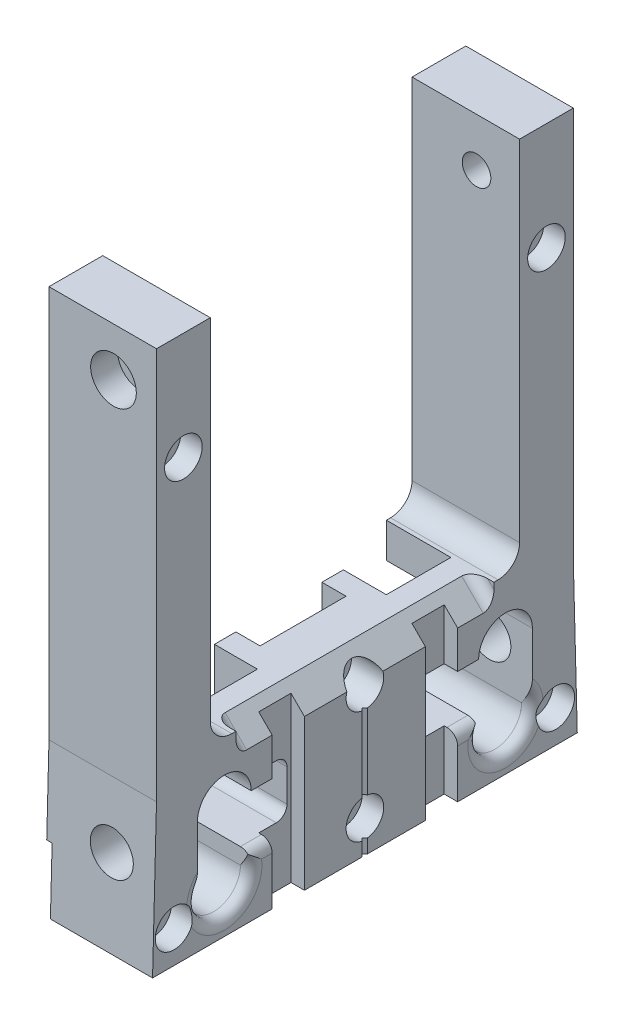
SolidWorks part; units mm, degrees
material "Nylatron"
ref_plane "Front Plane" through (0, 0, 0) normal (0, 0, 1) x (1, 0, 0)
ref_plane "Top Plane" through (0, 0, 0) normal (0, 1, 0) x (1, 0, 0)
ref_plane "Right Plane" through (0, 0, 0) normal (1, 0, 0) x (0, 0, -1)
sketch "Sketch1" plane through (0, 0, 0) normal (0, 0, 1) x (1, 0, 0)
  line L1 (-15.875, 80.1688) -> (15.875, 80.1688)
  line L2 (-15.875, 80.1688) -> (-15.875, -80.1688)
  line L3 (-15.875, -80.1688) -> (15.875, -80.1688)
  line L4 (15.875, 80.1688) -> (15.875, -80.1688)
  line L5 (-15.875, 80.1688) -> (15.875, -80.1688) construction
  line L6 (-15.875, -80.1688) -> (15.875, 80.1688) construction
  point P0 (0, 0)
  dimension "Width" = 31.75
  dimension "Height" = 160.3375
extrude "Extrude1" add sketch "Sketch1" along normal mid plane 125.4125
sketch "Sketch2" plane through (15.875, 0, 0) normal (1, 0, 0) x (0, 0, -1)
  line L0 (-62.7063, -80.1688) -> (-61.5423, -35.7188)
  line L1 (-62.7063, 80.1688) -> (62.7063, 80.1688) construction
  line L3 (62.7063, -80.1688) -> (61.5423, -35.7188)
  line L4 (62.7063, -80.1688) -> (62.7063, 80.1688) construction
  line L5 (-62.7063, -80.1688) -> (62.7063, -80.1688) construction
  line L6 (-61.5423, -35.7188) -> (-61.5423, 80.1688)
  line L7 (61.5423, 80.1688) -> (62.7063, 80.1688)
  line L8 (62.7063, 80.1688) -> (62.7063, -80.1688)
  line L9 (-62.7063, -80.1688) -> (-62.7063, 80.1688) construction
  line L10 (-61.5423, 80.1688) -> (-62.7063, 80.1688)
  line L11 (-62.7063, 80.1688) -> (-62.7063, -80.1688)
  line L12 (61.5423, -35.7188) -> (61.5423, 80.1688)
  dimension "D1" = 1.5
  dimension "D2" = 1.5
  dimension "D3" = 44.45
extrude "Extrude2" cut sketch "Sketch2" against normal through all
sketch "Sketch3" plane through (15.875, 0, 0) normal (1, 0, 0) x (0, 0, -1)
  line L0 (-19.0373, -59.5312) -> (-19.0373, -50.0063)
  line L1 (-49.4538, -46.8312) -> (-49.4538, -67.4688)
  line L2 (49.4538, -67.4688) -> (49.4538, -46.8313)
  line L3 (19.0373, -59.5312) -> (19.0373, -50.0063)
  line L4 (-22.2123, -62.7063) -> (-33.5788, -62.7062)
  line L5 (-22.2123, -46.8312) -> (-33.5788, -46.8313)
  line L6 (22.2123, -46.8312) -> (33.5788, -46.8312)
  line L8 (22.2123, -62.7063) -> (33.5788, -62.7062)
  line L9 (-33.5788, -62.7062) -> (-33.5788, -67.4688)
  line L10 (33.5788, -62.7062) -> (33.5788, -67.4688)
  line L11 (-62.7063, -80.1688) -> (62.7063, -80.1688) construction
  line L12 (-62.7063, -80.1688) -> (62.7063, -80.1688) construction
  line L13 (-19.0373, -54.7687) -> (19.0373, -54.7687) construction
  arc A0 (-19.0373, -50.0063) -> (-22.2123, -46.8312) centre (-22.2123, -50.0063) ccw
  arc A1 (33.5788, -67.4688) -> (49.4538, -67.4688) centre (41.5163, -67.4688) ccw
  arc A2 (-33.5788, -46.8313) -> (-49.4538, -46.8312) centre (-41.5163, -46.8312) ccw
  arc A3 (-19.0373, -59.5312) -> (-22.2123, -62.7063) centre (-22.2123, -59.5312) cw
  arc A4 (49.4538, -46.8313) -> (33.5788, -46.8312) centre (41.5163, -46.8313) ccw
  arc A5 (-49.4538, -67.4688) -> (-33.5788, -67.4688) centre (-41.5163, -67.4688) ccw
  arc A6 (22.2123, -62.7063) -> (19.0373, -59.5312) centre (22.2123, -59.5312) cw
  arc A7 (19.0373, -50.0063) -> (22.2123, -46.8312) centre (22.2123, -50.0063) cw
  point P0 (0, -54.7687)
  point P2 (-31.9913, -54.7687)
  point P5 (31.9913, -54.7687)
  point P23 (-19.0373, -62.7062)
  point P36 (-62.7063, -80.1688)
  point P38 (62.7063, -80.1688)
  dimension "D4" = 9.525
  dimension "D3" = 7.9375
  dimension "D7" = 7.9375
  dimension "D1" = 3.175
  dimension "D2" = 15.875
  dimension "D5" = 9.525
  dimension "D6" = 25.4
  dimension "D8" = 14.5415
  dimension "D9" = 21.1899
  dimension "D10" = 12.7
extrude "Extrude3" cut sketch "Sketch3" against normal up to next
sketch "Sketch15" plane through (0, 80.1688, 0) normal (0, 1, 0) x (1, 0, 0)
  line L0 (15.875, -61.5423) -> (15.875, 61.5423) construction
  line L1 (15.875, -27.3844) -> (11.9062, -27.3844)
  line L2 (15.875, -27.3844) -> (15.875, -17.8594)
  line L3 (15.875, -17.8594) -> (11.9062, -17.8594)
  line L4 (11.9062, -27.3844) -> (11.9062, -17.8594)
  line L5 (-15.875, -62.7063) -> (15.875, -62.7063) construction
  line L6 (15.875, 17.8594) -> (11.9062, 17.8594)
  line L7 (15.875, 17.8594) -> (15.875, 27.3844)
  line L8 (15.875, 27.3844) -> (11.9062, 27.3844)
  line L9 (11.9062, 17.8594) -> (11.9062, 27.3844)
  line L10 (-15.875, 62.7063) -> (15.875, 62.7063) construction
  dimension "D1" = 9.525
  dimension "D2" = 3.9688
  dimension "D3" = 35.3219
  dimension "D4" = 35.3219
extrude "Extrude6" cut sketch "Sketch15" against normal through all
sketch "Sketch16" plane through (15.875, 0, 0) normal (1, 0, 0) x (0, 0, -1)
  line L0 (-61.5423, 80.1688) -> (-27.3844, 80.1688) construction
  line L1 (-45.6673, 80.1688) -> (45.6673, 80.1688)
  line L2 (-45.6673, 80.1688) -> (-45.6673, -23.0187)
  line L3 (-39.3173, -29.3687) -> (39.3173, -29.3687)
  line L4 (45.6673, 80.1688) -> (45.6673, -23.0187)
  line L5 (-17.8594, -80.1688) -> (17.8594, -80.1688) construction
  line L6 (61.5423, 80.1688) -> (61.5423, -35.7188) construction
  line L7 (-61.5423, -35.7188) -> (-61.5423, 80.1688) construction
  arc A0 (39.3173, -29.3687) -> (45.6673, -23.0187) centre (39.3173, -23.0187) ccw
  arc A1 (-45.6673, -23.0187) -> (-39.3173, -29.3687) centre (-39.3173, -23.0187) ccw
  dimension "D4" = 6.35
  dimension "D1" = 50.8
  dimension "D2" = 15.875
  dimension "D3" = 15.875
extrude "Cut-Extrude1" cut sketch "Sketch16" against normal through all
sketch "Sketch17" plane through (0, 0, 0) normal (0, 0, 1) x (1, 0, 0)
  line L0 (-15.875, -35.7188) -> (-15.875, 80.1688) construction
  line L1 (-15.875, -60.9917) -> (-14.2875, -60.9917)
  line L2 (-15.875, -60.9917) -> (-15.875, -80.1688)
  line L3 (-15.875, -80.1688) -> (-14.2875, -80.1688)
  line L4 (-14.2875, -60.9917) -> (-14.2875, -80.1688)
  line L6 (-15.875, -80.1688) -> (15.875, -80.1688) construction
  dimension "D1" = 1.5875
  dimension "D2" = 19.177
extrude "Cut-Extrude2" cut sketch "Sketch17" against normal mid plane 193.675
hole_wizard "CBORE for 1/4 Socket Head Cap Screw4" positions "Sketch18" profile "Sketch19" counterbore size "1/4" standard "ANSI Inch" end condition up to next
sketch "Sketch18" plane through (15.875, 0, 0) normal (1, 0, 0) x (0, 0, -1)
  line L3 (-49.4538, -60.9917) -> (-62.2041, -60.9917) construction
  point P0 (-56.3563, -70.5802)
  point P2 (56.3563, -70.5802)
  point P14 (0, -70.5802)
  dimension "D1" = 9.5885
  dimension "D2" = 6.35
  dimension "D3" = 6.35
sketch "Sketch19" plane through (15.875, -70.5802, 56.3563) normal (0, 1, 0) x (0, 0, -1)
  line L0 (0, 0) -> (0, 30.1625)
  line L1 (0, 30.1625) -> (3.3782, 30.1625)
  line L3 (3.3782, 30.1625) -> (3.3782, 6.35)
  line L4 (3.3782, 6.35) -> (5.5562, 6.35)
  line L5 (5.5562, 6.35) -> (5.5562, 0)
  line L7 (5.5562, 0) -> (0, 0)
  line L11 (0, -6.35) -> (0, 107.95) construction
  dimension "Thru Hole Dia." = 6.7564
  dimension "Thru Hole Depth" = 30.1625
  dimension "C'Bore Dia." = 11.1125
  dimension "C'Bore Depth" = 6.35
hole_wizard "CBORE for 5/16 Socket Head Cap Screw2" positions "Sketch20" profile "Sketch21" counterbore size "5/16" standard "ANSI Inch" end condition up to next
sketch "Sketch20" plane through (0, 0, -61.5423) normal (0, 0, -1) x (-1, 0, 0)
  line L1 (-15.875, 80.1688) -> (-15.875, -35.7188) construction
  line L2 (15.875, 80.1688) -> (-15.875, 80.1688) construction
  point P0 (-3.175, 65.8812)
  dimension "D1" = 14.2875
  dimension "D2" = 12.7
sketch "Sketch21" plane through (3.175, 65.8812, -61.5423) normal (1, 0, 0) x (0, 1, 0)
  line L0 (0, 0) -> (0, 15.875)
  line L1 (0, 15.875) -> (4.2164, 15.875)
  line L3 (4.2164, 15.875) -> (4.2164, 7.9375)
  line L4 (4.2164, 7.9375) -> (6.7475, 7.9375)
  line L5 (6.7475, 7.9375) -> (6.7475, 0)
  line L7 (6.7475, 0) -> (0, 0)
  line L11 (0, -6.35) -> (0, 107.95) construction
  dimension "Thru Hole Dia." = 8.4328
  dimension "Thru Hole Depth" = 15.875
  dimension "C'Bore Dia." = 13.495
  dimension "C'Bore Depth" = 7.9375
hole_wizard "CBORE for 5/16 Socket Head Cap Screw3" positions "Sketch22" profile "Sketch23" counterbore size "5/16" standard "ANSI Inch" end condition up to next
sketch "Sketch22" plane through (0, 0, 61.5423) normal (0, 0, 1) x (1, 0, 0)
  point P0 (3.175, 65.8812)
sketch "Sketch23" plane through (3.175, 65.8812, 61.5423) normal (1, 0, 0) x (0, -1, 0)
  line L0 (0, 0) -> (0, 15.875)
  line L1 (0, 15.875) -> (4.2164, 15.875)
  line L3 (4.2164, 15.875) -> (4.2164, 7.9375)
  line L4 (4.2164, 7.9375) -> (6.7475, 7.9375)
  line L5 (6.7475, 7.9375) -> (6.7475, 0)
  line L7 (6.7475, 0) -> (0, 0)
  line L11 (0, -6.35) -> (0, 107.95) construction
  dimension "Thru Hole Dia." = 8.4328
  dimension "Thru Hole Depth" = 15.875
  dimension "C'Bore Dia." = 13.495
  dimension "C'Bore Depth" = 7.9375
hole_wizard "CBORE for 1/4 Socket Head Cap Screw2" positions "Sketch29" profile "Sketch30" counterbore size "1/4" standard "ANSI Inch" end condition up to next
sketch "Sketch29" plane through (15.875, 0, 0) normal (1, 0, 0) x (0, 0, -1)
  line L0 (45.6673, 80.1688) -> (61.5423, 80.1688) construction
  line L2 (53.6048, 80.1688) -> (53.6048, 48.4187) construction
  line L4 (-53.6048, 80.1687) -> (-53.6048, 48.4187) construction
  line L5 (-61.5423, 80.1688) -> (-45.6673, 80.1688) construction
  point P0 (53.6048, 48.4187)
  point P2 (-53.6048, 48.4187)
  dimension "D1" = 31.75
sketch "Sketch30" plane through (15.875, 48.4187, -53.6048) normal (0, 1, 0) x (0, 0, -1)
  line L0 (0, 0) -> (0, 31.75)
  line L1 (0, 31.75) -> (3.3782, 31.75)
  line L3 (3.3782, 31.75) -> (3.3782, 6.35)
  line L4 (3.3782, 6.35) -> (5.5562, 6.35)
  line L5 (5.5562, 6.35) -> (5.5562, 0)
  line L7 (5.5562, 0) -> (0, 0)
  line L11 (0, -6.35) -> (0, 107.95) construction
  dimension "Thru Hole Dia." = 6.7564
  dimension "Thru Hole Depth" = 31.75
  dimension "C'Bore Dia." = 11.1125
  dimension "C'Bore Depth" = 6.35
fillet "Fillet1" radius 3.175 2 edges at (15.875, -62.7063, -30.4816) (15.875, -62.7063, 30.4816)
ref_plane "Plane1" through (0, 0, 63.5) normal (0, 0, 1) x (1, 0, 0)
sketch "Sketch32" plane through (0, 0, 63.5) normal (0, 0, 1) x (1, 0, 0)
  line L0 (-14.2875, -80.1688) -> (15.875, -80.1688) construction
  line L2 (15.875, -35.7188) -> (15.875, 80.1688) construction
  circle A0 centre (3.175, -54.7687) radius 6.35
  dimension "D1" = 25.4
  dimension "D3" = 12.7
  dimension "D2" = 12.7
extrude "Cut-Extrude7" cut sketch "Sketch32" against normal blind 22.225
ref_plane "Plane2" through (0, 0, -63.5) normal (0, 0, 1) x (1, 0, 0)
sketch "Sketch33" plane through (0, 0, -63.5) normal (0, 0, 1) x (1, 0, 0)
  circle A0 centre (3.175, -54.7687) radius 6.35 construction
  circle A1 centre (3.175, -54.7687) radius 6.35
extrude "Cut-Extrude8" cut sketch "Sketch33" along normal blind 22.225
sketch "Sketch41" plane through (-15.875, 0, 0) normal (-1, 0, 0) x (0, 0, 1)
  line L1 (-38.0873, -29.2485) -> (-19.0373, -29.2485)
  line L2 (-38.0873, -29.2485) -> (-38.0873, -54.7688)
  line L3 (-38.0873, -54.7688) -> (-19.0373, -54.7688)
  line L4 (-19.0373, -29.2485) -> (-19.0373, -54.7688)
  line L5 (19.0373, -50.0063) -> (19.0373, -59.5312) construction
  line L6 (19.0373, -29.2485) -> (38.0873, -29.2485)
  line L7 (19.0373, -29.2485) -> (19.0373, -54.7688)
  line L8 (19.0373, -54.7688) -> (38.0873, -54.7687)
  line L9 (38.0873, -29.2485) -> (38.0873, -54.7687)
  line L10 (-19.0373, -59.5312) -> (-19.0373, -50.0063) construction
  arc A0 (-45.6673, -23.0187) -> (-39.3173, -29.3687) centre (-39.3173, -23.0187) ccw construction
  arc A1 (39.3173, -29.3687) -> (45.6673, -23.0187) centre (39.3173, -23.0187) ccw construction
  dimension "D1" = 19.05
  dimension "D2" = 19.05
extrude "Cut-Extrude9" cut sketch "Sketch41" against normal blind 19.05
sketch "Sketch43" plane through (0, -29.3687, 0) normal (0, 1, 0) x (1, 0, 0)
  line L0 (3.175, -19.0373) -> (-15.875, -19.0373) construction
  line L1 (-15.875, 19.0373) -> (-9.525, 19.0373)
  line L2 (-15.875, 19.0373) -> (-15.875, -19.0373)
  line L3 (-15.875, -19.0373) -> (-9.525, -19.0373)
  line L4 (-9.525, 19.0373) -> (-9.525, -19.0373)
  dimension "D1" = 6.35
extrude "Cut-Extrude11" cut sketch "Sketch43" against normal blind 22.225
sketch "Sketch44" plane through (-9.525, 0, 0) normal (-1, 0, 0) x (0, 0, 1)
  line L0 (19.0373, -29.3687) -> (-19.0373, -29.3687) construction
  line L1 (-12.7, -29.3687) -> (12.7, -29.3687)
  line L2 (-12.7, -29.3687) -> (-12.7, -42.8625)
  line L3 (-9.525, -46.0375) -> (9.525, -46.0375)
  line L4 (12.7, -29.3687) -> (12.7, -42.8625)
  arc A1 (9.525, -46.0375) -> (12.7, -42.8625) centre (9.525, -42.8625) ccw
  arc A2 (-12.7, -42.8625) -> (-9.525, -46.0375) centre (-9.525, -42.8625) ccw
  dimension "D4" = 3.175
  dimension "D1" = 16.6687
  dimension "D2" = 25.4
  dimension "D3" = 12.7
extrude "Cut-Extrude12" cut sketch "Sketch44" against normal blind 7.1437
hole_wizard "CBORE for 1/4 Socket Head Cap Screw5" positions "Sketch45" profile "Sketch47" counterbore size "1/4" standard "ANSI Inch" end condition up to next
sketch "Sketch45" plane through (15.875, 0, 0) normal (1, 0, 0) x (0, 0, -1)
  line L0 (-17.8594, -29.3687) -> (17.8594, -29.3688) construction
  point P0 (0, -37.3062)
  dimension "D1" = 7.9375
sketch "Sketch47" plane through (15.875, -37.3062, 0) normal (0, 1, 0) x (0, 0, -1)
  line L0 (0, 0) -> (0, 18.2562)
  line L1 (0, 18.2562) -> (3.3782, 18.2562)
  line L3 (3.3782, 18.2562) -> (3.3782, 9.525)
  line L4 (3.3782, 9.525) -> (5.5562, 9.525)
  line L5 (5.5562, 9.525) -> (5.5563, 0)
  line L7 (5.5563, 0) -> (0, 0)
  line L11 (0, -6.35) -> (0, 107.95) construction
  dimension "Thru Hole Dia." = 6.7564
  dimension "Thru Hole Depth" = 18.2562
  dimension "C'Bore Dia." = 11.1125
  dimension "C'Bore Depth" = 9.525
fillet "Fillet2" radius 3.175 1 edges at (15.875, -75.4062, -41.5163) tangent propagation no
fillet "Fillet3" radius 3.175 1 edges at (15.875, -75.4062, 41.5163) tangent propagation no
sketch "Sketch48" plane through (0, -80.1688, 0) normal (0, -1, 0) x (1, 0, 0)
  line L0 (15.875, 0.7937) -> (15.0812, 0)
  line L1 (15.875, 17.8594) -> (15.875, -17.8594) construction
  line L2 (15.0812, 0) -> (15.875, -0.7938)
  line L3 (15.875, -0.7938) -> (15.875, 0.7937)
  dimension "D1" = 1.5875
  dimension "D2" = 0.7937
  dimension "D3" = 0.7937
extrude "Cut-Extrude13" cut sketch "Sketch48" against normal through all
sketch "Sketch49" plane through (0, 0, 0) normal (0, 0, 1) x (1, 0, 0)
  line L0 (15.875, -29.3687) -> (9.525, -29.3687)
  line L1 (-15.875, -29.3687) -> (15.875, -29.3687) construction
  line L2 (9.525, -29.3687) -> (15.875, -35.7187)
  line L3 (15.875, -35.7188) -> (15.875, 80.1688) construction
  line L4 (15.875, -35.7187) -> (15.875, -29.3687)
  dimension "D1" = 6.35
  dimension "D2" = 45
extrude "Cut-Extrude14" cut sketch "Sketch49" against normal mid plane 76.2
fillet "Fillet4" radius 3.175 2 edges at (12.7, -32.5437, -38.1) (12.7, -32.5437, 38.1)
